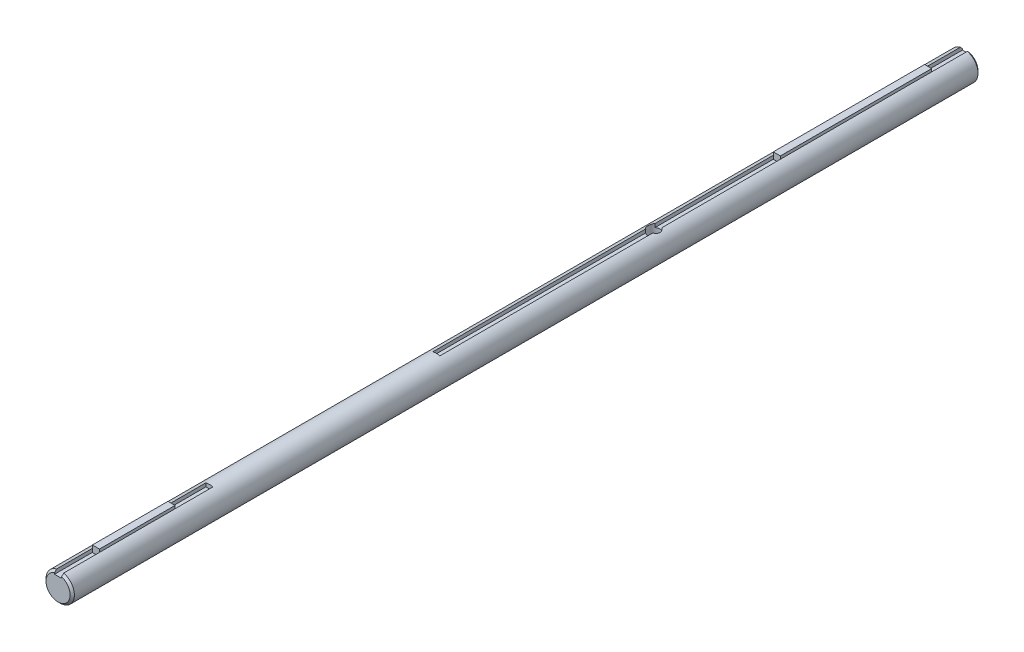
SolidWorks part; units mm, degrees
ref_plane "Front Plane" through (0, 0, 0) normal (0, 0, 1) x (1, 0, 0)
ref_plane "Top Plane" through (0, 0, 0) normal (0, 1, 0) x (1, 0, 0)
ref_plane "Right Plane" through (0, 0, 0) normal (1, 0, 0) x (0, 0, -1)
sketch "Sketch1" plane through (0, 0, 0) normal (0, 0, 1) x (1, 0, 0)
  line L0 (-2.3813, 6.8413) -> (2.3813, 6.8413)
  line L1 (-2.3813, 6.8413) -> (-2.3812, 9.2225)
  line L2 (2.3813, 6.8413) -> (2.3812, 9.2225)
  line L3 (-2.3812, 11.1792) -> (2.3812, 11.1792)
  line L4 (-2.3812, 11.1792) -> (-2.3812, 9.2225)
  line L5 (2.3812, 11.1792) -> (2.3812, 9.2225)
  circle A0 centre (0, 0) radius 9.525
  circle A1 centre (0, 0) radius 11.43 construction
  point P5 (0, 6.8413)
  point P11 (0, 9.525)
  dimension "Diameter" = 19.05
  dimension "D1" = 22.86
  dimension "Keyway Width" = 4.7625
  dimension "Keyway Depth" = 2.3813
  dimension "D2" = 4.7625
sketch "Sketch2" plane through (0, 0, 0) normal (1, 0, 0) x (0, 0, -1)
  line L0 (-304.8, 9.525) -> (304.8, 9.525)
  point P2 (-203.2, 9.525)
  point P3 (-50.8, 9.525)
  point P4 (-38.1, 9.525)
  point P5 (-279.4, 9.525)
  point P6 (-228.6, 9.525)
  point P7 (279.4, 9.525)
  point P8 (177.8, 9.525)
  point P9 (-171.45, 9.525)
  point P10 (171.45, 9.525)
  point P11 (-50.8, 9.525)
  point P12 (304.8, 9.525)
  point P13 (-63.5, 9.525)
  dimension "Length" = 609.6
  dimension "Key 1 Length" = 50.8
  dimension "D2" = 25.4
  dimension "Key 2 Length" = 101.6
  dimension "D3" = 133.35
  dimension "D4" = 133.35
  dimension "D5" = 12.7
  dimension "D6" = 12.7
sketch "Sketch3" plane through (0, 0, 0) normal (0, 0, 1) x (1, 0, 0)
  circle A0 centre (0, 0) radius 9.525 construction
  circle A1 centre (0, 0) radius 9.525
extrude "Boss-Extrude1" add sketch "Sketch3" along normal mid plane 609.6
chamfer "Chamfer1" distance 1.4287 angle 45 2 edges at (9.525, 0, -304.8) (9.525, 0, 304.8)
sketch "Sketch5" plane through (0, 0, 304.8) normal (0, 0, 1) x (1, 0, 0)
  line L0 (-2.3812, 11.1792) -> (2.3812, 11.1792) construction
  line L1 (2.3812, 11.1792) -> (2.3812, 9.2225) construction
  line L2 (2.3813, 6.8413) -> (2.3812, 9.2225) construction
  line L3 (-2.3813, 6.8413) -> (2.3813, 6.8413) construction
  line L4 (-2.3813, 6.8413) -> (-2.3812, 9.2225) construction
  line L5 (-2.3812, 11.1792) -> (-2.3812, 9.2225) construction
  line L6 (-2.3812, 11.1792) -> (2.3812, 11.1792)
  line L7 (2.3812, 11.1792) -> (2.3812, 9.2225)
  line L8 (2.3813, 6.8413) -> (2.3812, 9.2225)
  line L9 (-2.3813, 6.8413) -> (2.3813, 6.8413)
  line L10 (-2.3813, 6.8413) -> (-2.3812, 9.2225)
  line L11 (-2.3812, 11.1792) -> (-2.3812, 9.2225)
extrude "Cut-Extrude1" cut sketch "Sketch5" against normal up to vertex (101.6 mm away) up to point (0, 9.525, 203.2)
sketch "Sketch6" plane through (0, 0, -304.8) normal (0, 0, -1) x (-1, 0, 0)
  line L6 (2.3812, 11.1792) -> (-2.3812, 11.1792)
  line L7 (-2.3812, 11.1792) -> (-2.3812, 9.2225)
  line L8 (-2.3812, 9.2225) -> (-2.3813, 6.8413)
  line L9 (-2.3813, 6.8413) -> (2.3813, 6.8413)
  line L10 (2.3813, 6.8413) -> (2.3812, 9.2225)
  line L11 (2.3812, 9.2225) -> (2.3812, 11.1792)
  line L12 (2.3812, 11.1792) -> (-2.3812, 11.1792)
  line L13 (-2.3812, 11.1792) -> (-2.3812, 9.2225)
  line L14 (-2.3812, 9.2225) -> (-2.3813, 6.8413)
  line L15 (-2.3813, 6.8413) -> (2.3813, 6.8413)
  line L16 (2.3813, 6.8413) -> (2.3812, 9.2225)
  line L17 (2.3812, 9.2225) -> (2.3812, 11.1792)
  dimension "D1" = 0
extrude "Cut-Extrude2" cut sketch "Sketch6" against normal up to vertex (355.6 mm away) up to point (0, 9.525, 50.8)
ref_plane "Plane1" through (0, 0, 279.4) normal (0, 0, 1) x (1, 0, 0)
sketch "Sketch7" plane through (0, 0, 279.4) normal (0, 0, 1) x (1, 0, 0)
  line L0 (-2.3812, 11.1792) -> (-2.3812, 9.2225) construction
  line L1 (-2.3813, 6.8413) -> (-2.3812, 9.2225) construction
  line L2 (-2.3813, 6.8413) -> (2.3813, 6.8413) construction
  line L3 (2.3813, 6.8413) -> (2.3812, 9.2225) construction
  line L4 (2.3812, 11.1792) -> (2.3812, 9.2225) construction
  line L5 (-2.3812, 11.1792) -> (2.3812, 11.1792) construction
  line L6 (-2.3812, 11.1792) -> (-2.3812, 9.2225)
  line L7 (-2.3813, 6.8413) -> (-2.3812, 9.2225)
  line L8 (-2.3813, 6.8413) -> (2.3813, 6.8413)
  line L9 (2.3813, 6.8413) -> (2.3812, 9.2225)
  line L10 (2.3812, 11.1792) -> (2.3812, 9.2225)
  line L11 (-2.3812, 11.1792) -> (2.3812, 11.1792)
extrude "Boss-Extrude2" add sketch "Sketch7" against normal up to vertex (50.8 mm away) up to point (0, 9.525, 228.6)
ref_plane "Plane2" through (0, 0, -279.4) normal (0, 0, 1) x (1, 0, 0)
sketch "Sketch8" plane through (0, 0, -279.4) normal (0, 0, 1) x (1, 0, 0)
  line L0 (-2.3812, 11.1792) -> (-2.3812, 9.2225) construction
  line L1 (-2.3813, 6.8413) -> (-2.3812, 9.2225) construction
  line L2 (-2.3813, 6.8413) -> (2.3813, 6.8413) construction
  line L3 (2.3813, 6.8413) -> (2.3812, 9.2225) construction
  line L4 (2.3812, 11.1792) -> (2.3812, 9.2225) construction
  line L5 (-2.3812, 11.1792) -> (2.3812, 11.1792) construction
  line L6 (-2.3812, 11.1792) -> (-2.3812, 9.2225)
  line L7 (-2.3813, 6.8413) -> (-2.3812, 9.2225)
  line L8 (-2.3813, 6.8413) -> (2.3813, 6.8413)
  line L9 (2.3813, 6.8413) -> (2.3812, 9.2225)
  line L10 (2.3812, 11.1792) -> (2.3812, 9.2225)
  line L11 (-2.3812, 11.1792) -> (2.3812, 11.1792)
extrude "Boss-Extrude3" add sketch "Sketch8" along normal up to vertex (101.6 mm away) up to point (0, 9.525, -177.8)
sketch "Sketch9" plane through (0, 0, 0) normal (0, 1, 0) x (1, 0, 0)
  line L0 (2.3813, 304.8) -> (-2.3813, 304.8) construction
  line L1 (0, 95.25) -> (-9.525, 95.25) construction
  line L2 (-9.525, 303.3712) -> (-9.525, -303.3713) construction
  line L3 (0, 95.25) -> (9.525, 95.25) construction
  line L4 (9.525, -303.3713) -> (9.525, 303.3712) construction
  circle A1 centre (0, 95.25) radius 3.9687
  point P0 (0, 95.25)
  dimension "D2" = 7.9375
  dimension "D1" = 209.55
extrude "Cut-Extrude3" cut sketch "Sketch9" against normal through all both and the other way through all
equation "\"D1@Sketch1\"=\"Diameter@Sketch1\"*1.2"
equation "\"D1@Boss-Extrude1\"=\"length@sketch2\""
equation "\"D1@Chamfer1\"=\"Diameter@Sketch1\"*0.075"
equation "\"D4@Sketch2\"=\"D3@Sketch2\""
equation "\"D6@Sketch2\"=\"D5@Sketch2\""
